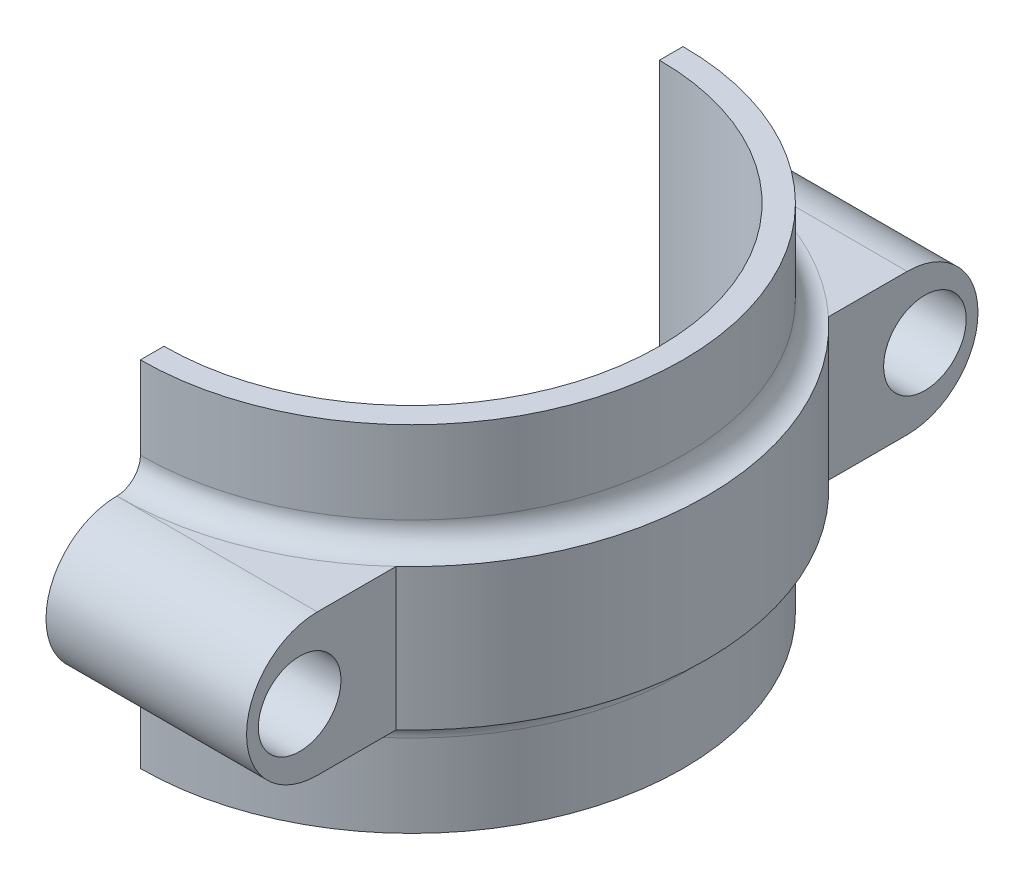
SolidWorks part; units mm, degrees
ref_plane "Front Plane" through (0, 0, 0) normal (0, 0, 1) x (1, 0, 0)
ref_plane "Top Plane" through (0, 0, 0) normal (0, 1, 0) x (1, 0, 0)
ref_plane "Right Plane" through (0, 0, 0) normal (1, 0, 0) x (0, 0, -1)
sketch "Sketch1" plane through (0, 0, 0) normal (0, 1, 0) x (1, 0, 0)
  line L0 (0, 21) -> (0, 31)
  line L1 (0, 31) -> (17, 31)
  line L2 (17, 31) -> (17, 18.3303)
  line L3 (0, 0) -> (50.0255, 0) construction
  line L4 (17, -31) -> (17, -18.3303)
  line L5 (0, -31) -> (17, -31)
  line L6 (0, -21) -> (0, -31)
  line L7 (0, 23) -> (0, 21)
  line L8 (0, -21) -> (0, -23)
  line L9 (0, 23) -> (0, 21)
  line L10 (0, -21) -> (0, -23)
  arc A0 (0, 21) -> (0, -21) centre (0, 0) cw
  arc A1 (17, 18.3303) -> (17, -18.3303) centre (0, 0) cw
  arc A2 (0, 23) -> (0, -23) centre (0, 0) cw
  dimension "D1" = 21
  dimension "D4" = 25
  dimension "D5" = 23
  dimension "D2" = 10
  dimension "D3" = 17
extrude "Boss-Extrude1" add sketch "Sketch1" along normal mid plane 12 contours L3 A2 L6 L5 L4 A1 | A2 L3 A1 L2 L1 L0 region at (11.6329, 0, -22.6734) region at (11.6329, 0, 22.6734)
extrude "Boss-Extrude2" add sketch "Sketch1<4>" along normal mid plane 30 contours A0 L3 A2 L0 | L3 A0 L6 A2 region at (0.3253, 0, -22) region at (22, 0, 0.3253)
sketch "Sketch1<4>" plane through (0, 0, 0) normal (0, 1, 0) x (1, 0, 0) same geometry as "Sketch1"
fillet "Fillet1" 2 edges at (8.5, 6, 31) (8.5, -6, 31) type full round first side face at (12.375, 6, 0) second side face at (12.375, -6, 0) middle face at (8.5, 0, 31)
fillet "Fillet2" 2 edges at (8.5, 6, -31) (8.5, -6, -31) type full round first side face at (12.375, 6, -1.5) second side face at (12.375, -6, -1.5) middle face at (8.5, 0, -31)
fillet "Fillet3" radius 2 2 edges at (23, -6, 0) (23, 6, 0)
sketch "Sketch2" plane through (0, 0, 0) normal (-1, 0, 0) x (0, 0, 1)
  line L0 (0, 15) -> (0, -15) construction
  line L1 (21, 15) -> (-21, 15) construction
  line L2 (-21, -15) -> (21, -15) construction
  circle A0 centre (-26.5, 0) radius 3.5
  circle A1 centre (26.5, 0) radius 3.5
  dimension "D2" = 7
  dimension "D1" = 26.5
extrude "Cut-Extrude1" cut sketch "Sketch2" against normal through all
